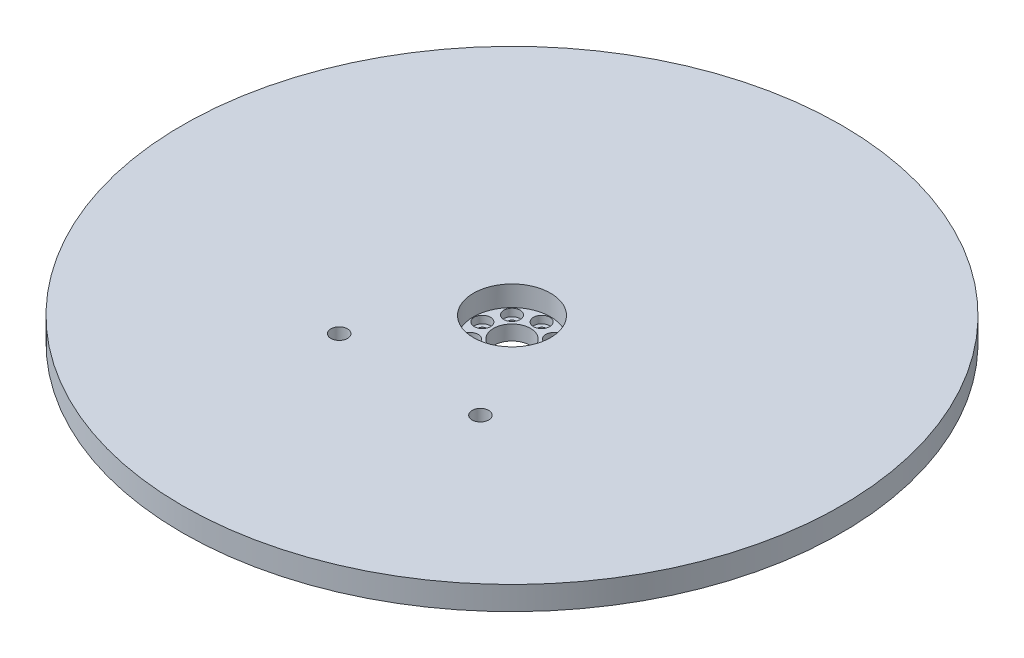
SolidWorks part; units mm, degrees
other "Markup1"
sketch "Sketch21" plane through (-65.5, -15.05, -60) normal (-0.0927, -0.2854, -0.9539) x (0.9951, -0.0609, -0.0785)
material "6061 Alloy"
ref_plane "Front Plane" through (0, 0, 0) normal (0, 0, 1) x (1, 0, 0)
ref_plane "Top Plane" through (0, 0, 0) normal (0, 1, 0) x (1, 0, 0)
ref_plane "Right Plane" through (0, 0, 0) normal (1, 0, 0) x (0, 0, -1)
sketch "Sketch1" plane through (0, 0, 0) normal (0, 1, 0) x (1, 0, 0)
  circle A0 centre (0, 0) radius 88.9
  dimension "D1" = 177.8
extrude "Boss-Extrude1" add sketch "Sketch1" along normal mid plane 6.35
sketch "Sketch2" plane through (0, -3.175, 0) normal (0, -1, 0) x (1, 0, 0)
  circle A0 centre (0, 0) radius 12.065
  circle A1 centre (0, 0) radius 88.9 construction
  dimension "D1" = 24.13
extrude "Boss-Extrude2" add sketch "Sketch2" along normal blind 3.175
sketch "Sketch5" plane through (0, 3.175, 0) normal (0, 1, 0) x (1, 0, 0)
  circle A0 centre (0, 0) radius 10.4
  circle A1 centre (0, 0) radius 88.9 construction
  dimension "D1" = 20.8
extrude "Cut-Extrude1" cut sketch "Sketch5" against normal offset from surface (5.525 mm away) 4 up to face at (0, -6.35, -12.065)
sketch "Sketch6" plane through (0, -2.35, 0) normal (0, 1, 0) x (1, 0, 0)
  circle A0 centre (0, 0) radius 5
  circle A1 centre (0, 0) radius 10.4 construction
  dimension "D1" = 10
extrude "Cut-Extrude2" cut sketch "Sketch6" along direction (0, -1, 0) on the side against the normal up to next (4 mm away)
sketch "Sketch15" plane through (0, -6.35, 0) normal (0, 1, 0) x (1, 0, 0)
  circle A0 centre (0, 8) radius 1
  circle A1 centre (-5.6569, 5.6569) radius 1
  circle A2 centre (5.6569, 5.6569) radius 1
  circle A3 centre (-5.6569, -5.6569) radius 1
  circle A4 centre (5.6569, -5.6569) radius 1
  circle A5 centre (-8, 0) radius 1
  circle A6 centre (0, -8) radius 1
  circle A7 centre (8, 0) radius 1
  circle A8 centre (0, 0) radius 4
  circle A9 centre (0, 0) radius 11
  circle A10 centre (0, 0) radius 2.25
  circle A11 centre (0, 0) radius 5
  circle A12 centre (0, 0) radius 5 construction
  dimension "D1" = 4.5
  dimension "D2" = 8
  dimension "D3" = 10
  dimension "D4" = 22
  dimension "D5" = 2
  dimension "D6" = 8
  dimension "D7" = 5.6569
  dimension "D8" = 8
  dimension "D9" = 5.6569
  dimension "D10" = 5.6569
  dimension "D11" = 8
  dimension "D12" = 5.6569
  dimension "D13" = 8
hole_wizard "CBORE for M2 SHCS1" positions "Sketch19" profile "Sketch20" counterbore size "M2" standard "ANSI Metric"
sketch "Sketch19" plane through (0, -2.35, 0) normal (0, 1, 0) x (1, 0, 0)
  point P0 (-5.6569, 5.6569)
  point P3 (0, 8)
  point P6 (5.6569, 5.6569)
  point P9 (8, 0)
  point P12 (5.6569, -5.6569)
  point P15 (0, -8)
  point P18 (-5.6569, -5.6569)
  point P21 (-8, 0)
sketch "Sketch20" plane through (-5.6569, -2.35, -5.6569) normal (1, 0, 0) x (0, 0, 1)
  line L0 (0, 0) -> (0, 6.6609)
  line L1 (0, 6.6609) -> (1.1, 6)
  line L2 (1.1, 6) -> (1.1, 2)
  line L3 (1.1, 2) -> (2.2, 2)
  line L4 (2.2, 2) -> (2.2, 0)
  line L5 (2.2, 0) -> (0, 0)
  line L10 (0, 6.6609) -> (-1.1, 6) construction
  line L11 (0, -6.35) -> (0, 107.95) construction
  dimension "Hole Dia." = 2.2
  dimension "Hole Depth" = 6
  dimension "C'Bore Dia." = 4.4
  dimension "C'Bore Depth" = 2
  dimension "Drill Angle" = 118
hole_wizard "M4 Clearance Hole1" positions "Sketch26" profile "Sketch27" hole size "M4" standard "ANSI Metric" end condition through all
sketch "Sketch26" plane through (0, 3.175, 0) normal (0, 1, 0) x (1, 0, 0)
  point P0 (19.05, -27.5642)
  point P3 (-19.05, -27.5642)
sketch "Sketch27" plane through (19.05, 3.175, 27.5642) normal (1, 0, 0) x (0, 0, 1)
  line L0 (0, 0) -> (0, 9.525)
  line L1 (0, 9.525) -> (2.25, 9.525)
  line L2 (2.25, 9.525) -> (2.25, 0)
  line L5 (2.25, 0) -> (0, 0)
  line L11 (0, -6.35) -> (0, 107.95) construction
  dimension "Thru Hole Dia." = 4.5
  dimension "Thru Hole Depth" = 9.525
